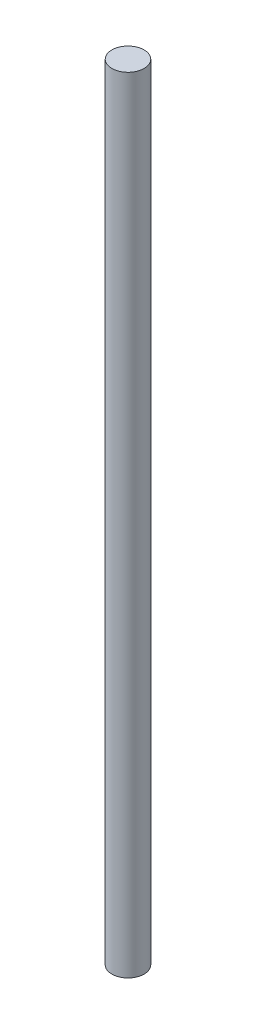
SolidWorks part; units mm, degrees
ref_plane "Front Plane" through (0, 0, 0) normal (0, 0, 1) x (1, 0, 0)
ref_plane "Top Plane" through (0, 0, 0) normal (0, 1, 0) x (1, 0, 0)
ref_plane "Right Plane" through (0, 0, 0) normal (1, 0, 0) x (0, 0, -1)
sketch "Sketch1" plane through (0, 0, 0) normal (0, 1, 0) x (1, 0, 0)
  circle A0 centre (0, 0) radius 2
  dimension "D1" = 4
extrude "Boss-Extrude1" add sketch "Sketch1" along normal blind 97.4
